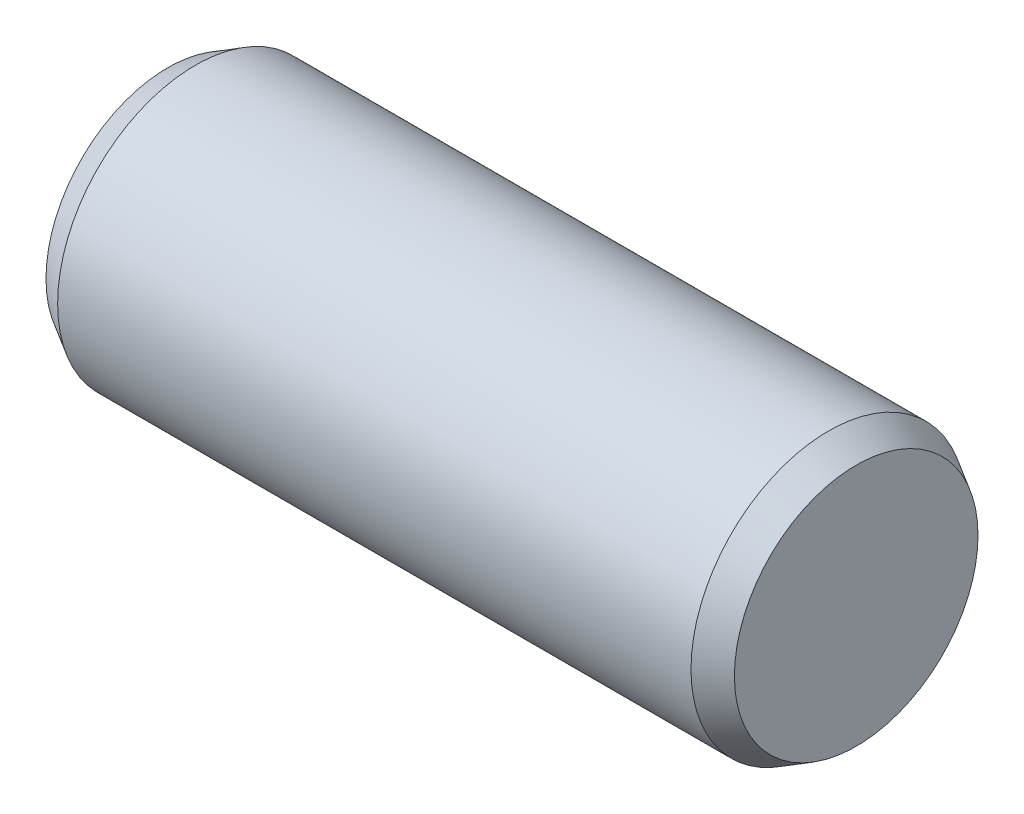
SolidWorks part; units mm, degrees
ref_plane "Front Plane" through (0, 0, 0) normal (0, 0, 1) x (1, 0, 0)
ref_plane "Top Plane" through (0, 0, 0) normal (0, 1, 0) x (1, 0, 0)
ref_plane "Right Plane" through (0, 0, 0) normal (1, 0, 0) x (0, 0, -1)
sketch "BodySke" plane through (0, 0, 0) normal (0, 0, 1) x (1, 0, 0)
  line L0 (0, 0) -> (123.0489, 0) construction
  line L1 (0, 0) -> (0, 17.6906)
  line L2 (0, 17.6906) -> (4, 20)
  line L3 (4, 20) -> (96, 20)
  line L4 (96, 20) -> (100, 17.6906)
  line L5 (100, 17.6906) -> (100, 0)
  line L6 (100, 0) -> (0, 0)
  circle A0 centre (10, 0) radius 4 construction
  circle A1 centre (90, 0) radius 4 construction
  dimension "D1" = 10
revolve "BaseBody" add sketch "BodySke" angle 360 about L0
sketch "HoleSke" plane through (0, 0, 0) normal (0, 0, 1) x (1, 0, 0)
  line L0 (0, 0) -> (103.0888, 0) construction
  line L1 (0, 17.6906) -> (0, -17.6906) construction
  circle A0 centre (90, 0) radius 4 construction
  circle A1 centre (10, 0) radius 4 construction
  circle A2 centre (90, 0) radius 4
  circle A3 centre (10, 0) radius 4
extrude "Hole" [suppressed] cut sketch "HoleSke" against normal through all and the other way through all
equation "\"D1@BodySke\" = \"Hole_height@BodySke\""
